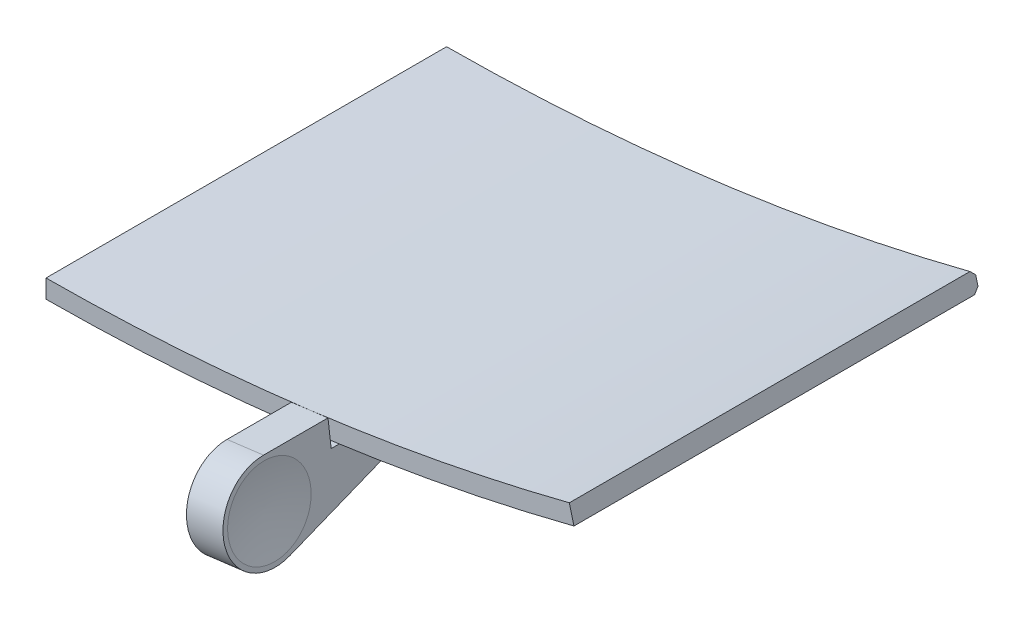
SolidWorks part; units mm, degrees
ref_plane "前视基准面" through (0, 0, 0) normal (0, 0, 1) x (1, 0, 0)
ref_plane "上视基准面" through (0, 0, 0) normal (0, 1, 0) x (1, 0, 0)
ref_plane "右视基准面" through (0, 0, 0) normal (1, 0, 0) x (0, 0, -1)
other "Configuration Table"
sketch "草图1" plane through (0, 0, 0) normal (0, 0, 1) x (1, 0, 0)
  line L0 (0, -235) -> (0, -237)
  line L1 (59.1966, -227.422) -> (59.7004, -229.3575)
  arc A0 (0, -235) -> (59.1966, -227.422) centre (0, 0) ccw
  arc A1 (0, -237) -> (59.7004, -229.3575) centre (0, 0) ccw
  dimension "D1" = 470
  dimension "D2" = 474
  dimension "D3" = 14.59
  dimension "D4" = 2
extrude "凸台-拉伸1" add sketch "草图1" along normal blind 44
chamfer "倒角1" distance 0.5 angle 45 4 edges at (0, -236, 0) (30.0938, -235.0816, 0) (59.4485, -228.3897, 0) (29.8398, -233.0978, 0)
sketch "草图4" plane through (0, 0, 44) normal (0, 0, 1) x (1, 0, 0)
  line L0 (1.2, -234.9969) -> (1.2, -236.997)
  line L1 (59.7004, -229.3575) -> (59.1966, -227.422)
  line L2 (58.0345, -227.7213) -> (58.5383, -229.6568)
  line L3 (0, -235) -> (0, -237)
  line L4 (59.7004, -229.3575) -> (59.1966, -227.422)
  line L5 (0, -235) -> (0, -237)
  arc A0 (0, -235) -> (59.1966, -227.422) centre (0, 0) ccw construction
  arc A1 (0, -237) -> (59.7004, -229.3575) centre (0, 0) ccw construction
  arc A2 (58.0345, -227.7213) -> (59.1966, -227.422) centre (0, 0) ccw
  arc A3 (58.5383, -229.6568) -> (59.7004, -229.3575) centre (0, 0) ccw
  arc A4 (0, -235) -> (59.1966, -227.422) centre (0, 0) ccw
  arc A5 (0, -237) -> (59.7004, -229.3575) centre (0, 0) ccw
  arc A6 (0, -235) -> (1.2, -234.9969) centre (0, 0) ccw
  arc A7 (0, -237) -> (1.2, -236.997) centre (0, 0) ccw
  dimension "D1" = 0
  dimension "D2" = 1.2
  dimension "D3" = 1.2
extrude "切除-拉伸1" cut sketch "草图4" against normal through all
ref_plane "基准面4" through (0, 0, 0) normal (-0.9919, -0.127, 0) x (0, 0, 1)
sketch "草图5" plane through (0, 0, 0) normal (-0.9919, -0.127, 0) x (0, 0, 1)
  line L0 (44, -235) -> (51, -235)
  line L1 (29, -237.731) -> (49.3759, -244.7289)
  line L2 (29, -237.731) -> (44, -237.731)
  line L3 (44, -237.731) -> (44, -235)
  line L6 (44, -235.231) -> (44, -233.2471) construction
  arc A0 (49.3759, -244.7289) -> (51, -235) centre (51, -240) ccw
  dimension "D1" = 10
  dimension "D2" = 2.5
  dimension "D3" = 15
  dimension "D4" = 7
extrude "凸台-拉伸3" add sketch "草图5" along normal blind 2 and the other way blind 2
ref_plane "基准面5" through (31.1096, -243.0169, 0) normal (0.127, -0.9919, 0) x (-0.9919, -0.127, 0)
ref_plane "基准面6" through (30.4747, -238.0573, 0) normal (0.127, -0.9919, 0) x (-0.9919, -0.127, 0)
sketch "草图6" plane through (30.4747, -238.0573, 0) normal (0.127, -0.9919, 0) x (-0.9919, -0.127, 0)
  line L0 (2, -51) -> (50002, -51) construction
  line L2 (-2, -56) -> (2, -56) construction
  line L3 (-2, -51) -> (-2, -55.5)
  line L4 (-2, -49.3759) -> (-2, -56) construction
  line L5 (-2, -51) -> (-1.4, -51)
  line L6 (0, -56) -> (0, 49944) construction
  line L7 (-2, -51) -> (-50002, -51) construction
  line L8 (2, -51) -> (1.4, -51)
  line L9 (2, -51) -> (2, -55.5)
  arc A0 (-2, -55.5) -> (-1.4, -51) centre (-21.3965, -50.6238) ccw
  arc A1 (2, -55.5) -> (1.4, -51) centre (21.3965, -50.6238) cw
  point P13 (0, -56)
  dimension "D2" = 20
  dimension "D1" = 5
  dimension "D3" = 0.6
  dimension "D4" = 4.5
revolve "切除-旋转2" cut sketch "草图6" angle 360 about L0
